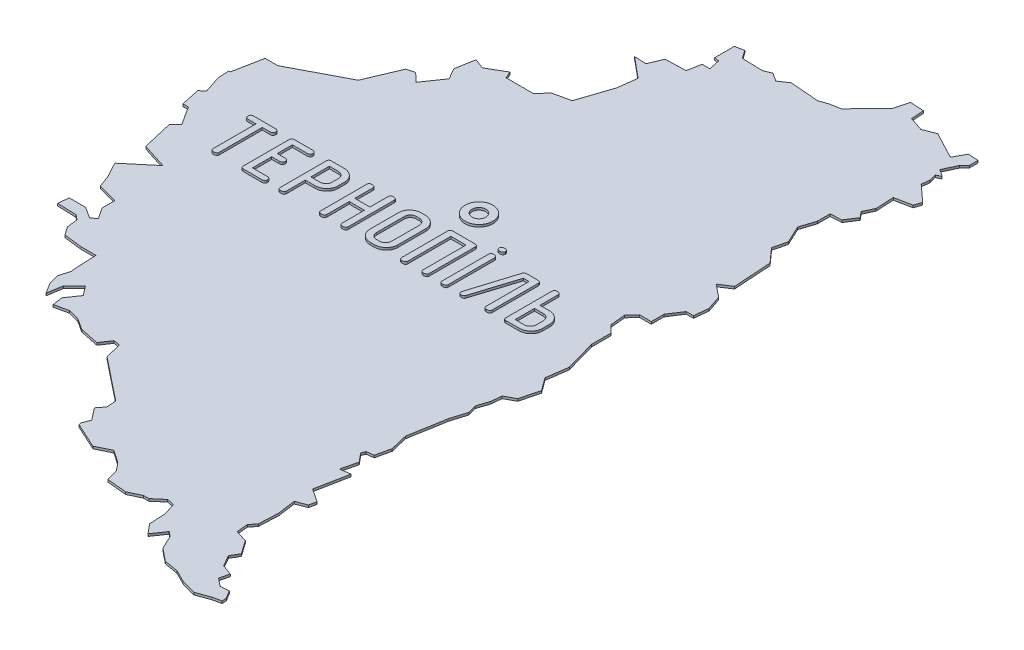
SolidWorks part; units mm, degrees
ref_plane "Спереди" through (0, 0, 0) normal (0, 0, 1) x (1, 0, 0)
ref_plane "Сверху" through (0, 0, 0) normal (0, 1, 0) x (1, 0, 0)
ref_plane "Справа" through (0, 0, 0) normal (1, 0, 0) x (0, 0, -1)
sketch "Эскиз1" plane through (0, 0, 0) normal (0, 1, 0) x (1, 0, 0)
  line B0 (-3330.514, 5782.4218) -> (-3349.3177, 5781.1264)
  line B1 (-3349.3177, 5781.1264) -> (-3366.1909, 5794.7458)
  line B2 (-3366.1909, 5794.7458) -> (-3361.0067, 5814.8703)
  line B3 (-3361.0067, 5814.8703) -> (-3383.7245, 5823.3081)
  line B4 (-3383.7245, 5823.3081) -> (-3397.344, 5847.2959)
  line B5 (-3397.344, 5847.2959) -> (-3386.9528, 5864.8295)
  line B6 (-3386.9528, 5864.8295) -> (-3407.0773, 5893.3918)
  line B7 (-3407.0773, 5893.3918) -> (-3433.0208, 5901.8272)
  line B8 (-3433.0208, 5901.8272) -> (-3434.9792, 5925.8149)
  line B9 (-3434.9792, 5925.8149) -> (-3424.5855, 5939.4598)
  line B10 (-3424.5855, 5939.4598) -> (-3422.6551, 5980.3208)
  line B11 (-3422.6551, 5980.3208) -> (-3427.8392, 6019.9372)
  line B12 (-3427.8392, 6019.9372) -> (-3405.7819, 6028.3471)
  line B13 (-3405.7819, 6028.3471) -> (-3402.5281, 6043.9249)
  line B14 (-3402.5281, 6043.9249) -> (-3431.0904, 6062.7539)
  line B15 (-3431.0904, 6062.7539) -> (-3417.4455, 6132.2001)
  line B16 (-3417.4455, 6132.2001) -> (-3439.5283, 6128.9489)
  line B17 (-3439.5283, 6128.9489) -> (-3431.0904, 6163.3303)
  line B18 (-3431.0904, 6163.3303) -> (-3446.6682, 6182.1593)
  line B19 (-3446.6682, 6182.1593) -> (-3443.4145, 6190.5947)
  line B20 (-3443.4145, 6190.5947) -> (-3427.8392, 6192.5276)
  line B21 (-3427.8392, 6192.5276) -> (-3420.6967, 6224.3411)
  line B22 (-3420.6967, 6224.3411) -> (-3429.7696, 6261.9738)
  line B23 (-3429.7696, 6261.9738) -> (-3420.6967, 6313.2538)
  line B24 (-3420.6967, 6313.2538) -> (-3416.1755, 6340.4928)
  line B25 (-3416.1755, 6340.4928) -> (-3405.7819, 6374.8996)
  line B26 (-3405.7819, 6374.8996) -> (-3410.966, 6393.7032)
  line B27 (-3410.966, 6393.7032) -> (-3402.5281, 6419.0118)
  line B28 (-3402.5281, 6419.0118) -> (-3400.5723, 6441.0946)
  line B29 (-3400.5723, 6441.0946) -> (-3378.5404, 6453.4186)
  line B30 (-3378.5404, 6453.4186) -> (-3368.1492, 6494.2796)
  line B31 (-3368.1492, 6494.2796) -> (-3388.2482, 6521.5465)
  line B32 (-3388.2482, 6521.5465) -> (-3381.7687, 6567.6399)
  line B33 (-3381.7687, 6567.6399) -> (-3400.5723, 6634.4698)
  line B34 (-3400.5723, 6634.4698) -> (-3400.5723, 6676.6542)
  line B35 (-3400.5723, 6676.6542) -> (-3416.1755, 6692.204)
  line B36 (-3416.1755, 6692.204) -> (-3419.4013, 6724.6551)
  line B37 (-3419.4013, 6724.6551) -> (-3403.8261, 6741.5258)
  line B38 (-3403.8261, 6741.5258) -> (-3378.5404, 6741.5258)
  line B39 (-3378.5404, 6741.5258) -> (-3378.5404, 6768.7927)
  line B40 (-3378.5404, 6768.7927) -> (-3359.7113, 6797.9849)
  line B41 (-3359.7113, 6797.9849) -> (-3344.1107, 6797.9849)
  line B42 (-3344.1107, 6797.9849) -> (-3340.8823, 6828.4852)
  line B43 (-3340.8823, 6828.4852) -> (-3351.276, 6859.6459)
  line B44 (-3351.276, 6859.6459) -> (-3378.5404, 6881.7185)
  line B45 (-3378.5404, 6881.7185) -> (-3354.5018, 6897.2735)
  line B46 (-3354.5018, 6897.2735) -> (-3359.7113, 6979.0513)
  line B47 (-3359.7113, 6979.0513) -> (-3386.9528, 7009.5516)
  line B48 (-3386.9528, 7009.5516) -> (-3379.8129, 7038.7616)
  line B49 (-3379.8129, 7038.7616) -> (-3397.344, 7076.3867)
  line B50 (-3397.344, 7076.3867) -> (-3386.9528, 7108.8428)
  line B51 (-3386.9528, 7108.8428) -> (-3386.9528, 7136.0767)
  line B52 (-3386.9528, 7136.0767) -> (-3362.9651, 7137.3924)
  line B53 (-3362.9651, 7137.3924) -> (-3347.3873, 7161.4005)
  line B54 (-3347.3873, 7161.4005) -> (-3357.7555, 7173.7449)
  line B55 (-3357.7555, 7173.7449) -> (-3347.3873, 7195.7921)
  line B56 (-3347.3873, 7195.7921) -> (-3349.3177, 7234.7379)
  line B57 (-3349.3177, 7234.7379) -> (-3313.6154, 7241.8677)
  line B58 (-3313.6154, 7241.8677) -> (-3308.4338, 7257.4455)
  line B59 (-3308.4338, 7257.4455) -> (-3344.1107, 7289.8914)
  line B60 (-3344.1107, 7289.8914) -> (-3342.1777, 7306.7494)
  line B61 (-3342.1777, 7306.7494) -> (-3346.0665, 7322.3349)
  line B62 (-3346.0665, 7322.3349) -> (-3335.6982, 7326.8611)
  line B63 (-3335.6982, 7326.8611) -> (-3351.276, 7337.2599)
  line B64 (-3351.276, 7337.2599) -> (-3337.6311, 7366.4775)
  line B65 (-3337.6311, 7366.4775) -> (-3327.2628, 7376.8509)
  line B66 (-3327.2628, 7376.8509) -> (-3327.2628, 7395.6596)
  line B67 (-3327.2628, 7395.6596) -> (-3349.3177, 7396.9677)
  line B68 (-3349.3177, 7396.9677) -> (-3362.9651, 7371.6515)
  line B69 (-3362.9651, 7371.6515) -> (-3420.6967, 7402.1518)
  line B70 (-3420.6967, 7402.1518) -> (-3446.6682, 7391.7708)
  line B71 (-3446.6682, 7391.7708) -> (-3477.1609, 7402.1518)
  line B72 (-3477.1609, 7402.1518) -> (-3479.1167, 7429.4136)
  line B73 (-3479.1167, 7429.4136) -> (-3508.3217, 7431.3542)
  line B74 (-3508.3217, 7431.3542) -> (-3516.757, 7400.8666)
  line B75 (-3516.757, 7400.8666) -> (-3571.2629, 7344.3973)
  line B76 (-3571.2629, 7344.3973) -> (-3593.3253, 7340.5111)
  line B77 (-3593.3253, 7340.5111) -> (-3612.1391, 7334.0138)
  line B78 (-3612.1391, 7334.0138) -> (-3673.79, 7339.2005)
  line B79 (-3673.79, 7339.2005) -> (-3693.9118, 7325.5759)
  line B80 (-3693.9118, 7325.5759) -> (-3711.4353, 7337.2599)
  line B81 (-3711.4353, 7337.2599) -> (-3728.3136, 7330.7651)
  line B82 (-3728.3136, 7330.7651) -> (-3772.4309, 7332.0656)
  line B83 (-3772.4309, 7332.0656) -> (-3784.7651, 7349.5789)
  line B84 (-3784.7651, 7349.5789) -> (-3803.5814, 7345.7003)
  line B85 (-3803.5814, 7345.7003) -> (-3803.5814, 7303.5058)
  line B86 (-3803.5814, 7303.5058) -> (-3793.1827, 7301.5704)
  line B87 (-3793.1827, 7301.5704) -> (-3788.0112, 7277.5674)
  line B88 (-3788.0112, 7277.5674) -> (-3804.8641, 7277.5674)
  line B89 (-3804.8641, 7277.5674) -> (-3810.066, 7248.3523)
  line B90 (-3810.066, 7248.3523) -> (-3854.1858, 7247.0594)
  line B91 (-3854.1858, 7247.0594) -> (-3866.5175, 7217.8494)
  line B92 (-3866.5175, 7217.8494) -> (-3892.4789, 7219.1524)
  line B93 (-3892.4789, 7219.1524) -> (-3886.6521, 7214.5982)
  line B94 (-3886.6521, 7214.5982) -> (-3847.7114, 7182.165)
  line B95 (-3847.7114, 7182.165) -> (-3852.9057, 7141.2862)
  line B96 (-3852.9057, 7141.2862) -> (-3876.9112, 7069.2467)
  line B97 (-3876.9112, 7069.2467) -> (-3914.5439, 7060.8114)
  line B98 (-3914.5439, 7060.8114) -> (-3931.4272, 7040.6946)
  line B99 (-3931.4272, 7040.6946) -> (-3991.102, 7040.6946)
  line B100 (-3991.102, 7040.6946) -> (-3997.6095, 7055.6145)
  line B101 (-3997.6095, 7055.6145) -> (-4035.2497, 7033.5673)
  line B102 (-4035.2497, 7033.5673) -> (-4057.3046, 7041.99)
  line B103 (-4057.3046, 7041.99) -> (-4064.4547, 7001.0985)
  line B104 (-4064.4547, 7001.0985) -> (-4050.825, 6977.1006)
  line B105 (-4050.825, 6977.1006) -> (-4080.0249, 6934.9087)
  line B106 (-4080.0249, 6934.9087) -> (-4098.8488, 6953.0824)
  line B107 (-4098.8488, 6953.0824) -> (-4115.7068, 6948.5383)
  line B108 (-4115.7068, 6948.5383) -> (-4146.2096, 6876.5166)
  line B109 (-4146.2096, 6876.5166) -> (-4260.4258, 6816.7987)
  line B110 (-4260.4258, 6816.7987) -> (-4287.6826, 6816.7987)
  line B111 (-4287.6826, 6816.7987) -> (-4300.0117, 6753.8498)
  line B112 (-4300.0117, 6753.8498) -> (-4303.2655, 6753.8498)
  line B113 (-4303.2655, 6753.8498) -> (-4301.9523, 6729.8367)
  line B114 (-4301.9523, 6729.8367) -> (-4289.6307, 6692.204)
  line B115 (-4289.6307, 6692.204) -> (-4300.0117, 6683.7941)
  line B116 (-4300.0117, 6683.7941) -> (-4291.5688, 6642.9077)
  line B117 (-4291.5688, 6642.9077) -> (-4279.2523, 6642.9077)
  line B118 (-4279.2523, 6642.9077) -> (-4270.817, 6629.2628)
  line B119 (-4270.817, 6629.2628) -> (-4253.9336, 6603.3167)
  line B120 (-4253.9336, 6603.3167) -> (-4267.5632, 6589.6973)
  line B121 (-4267.5632, 6589.6973) -> (-4251.9829, 6523.4769)
  line B122 (-4251.9829, 6523.4769) -> (-4197.4643, 6505.9941)
  line B123 (-4197.4643, 6505.9941) -> (-4253.9336, 6458.6028)
  line B124 (-4253.9336, 6458.6028) -> (-4237.068, 6427.4497)
  line B125 (-4237.068, 6427.4497) -> (-4226.6845, 6400.1828)
  line B126 (-4226.6845, 6400.1828) -> (-4183.855, 6388.5191)
  line B127 (-4183.855, 6388.5191) -> (-4183.855, 6361.2547)
  line B128 (-4183.855, 6361.2547) -> (-4168.2594, 6337.267)
  line B129 (-4168.2594, 6337.267) -> (-4178.6607, 6328.8037)
  line B130 (-4178.6607, 6328.8037) -> (-4202.6865, 6344.3815)
  line B131 (-4202.6865, 6344.3815) -> (-4238.3659, 6344.3815)
  line B132 (-4238.3659, 6344.3815) -> (-4240.2963, 6321.6638)
  line B133 (-4240.2963, 6321.6638) -> (-4199.4226, 6320.3684)
  line B134 (-4199.4226, 6320.3684) -> (-4189.034, 6311.933)
  line B135 (-4189.034, 6311.933) -> (-4185.7955, 6287.9199)
  line B136 (-4185.7955, 6287.9199) -> (-4173.4689, 6270.4116)
  line B137 (-4173.4689, 6270.4116) -> (-4134.5206, 6265.8625)
  line B138 (-4134.5206, 6265.8625) -> (-4102.0771, 6265.8625)
  line B139 (-4102.0771, 6265.8625) -> (-4100.134, 6224.3411)
  line B140 (-4100.134, 6224.3411) -> (-4098.8488, 6209.3983)
  line B141 (-4098.8488, 6209.3983) -> (-4105.341, 6185.3851)
  line B142 (-4105.341, 6185.3851) -> (-4098.8488, 6163.3303)
  line B143 (-4098.8488, 6163.3303) -> (-4085.2242, 6141.2476)
  line B144 (-4085.2242, 6141.2476) -> (-4080.0249, 6173.7215)
  line B145 (-4080.0249, 6173.7215) -> (-4056.0269, 6197.0996)
  line B146 (-4056.0269, 6197.0996) -> (-4040.4466, 6176.9498)
  line B147 (-4040.4466, 6176.9498) -> (-4059.2527, 6149.7083)
  line B148 (-4059.2527, 6149.7083) -> (-4056.0269, 6127.6535)
  line B149 (-4056.0269, 6127.6535) -> (-4026.8119, 6134.1076)
  line B150 (-4026.8119, 6134.1076) -> (-4002.7936, 6127.6535)
  line B151 (-4002.7936, 6127.6535) -> (-3978.7906, 6112.0757)
  line B152 (-3978.7906, 6112.0757) -> (-3937.8992, 6103.6403)
  line B153 (-3937.8992, 6103.6403) -> (-3922.9767, 6125.6951)
  line B154 (-3922.9767, 6125.6951) -> (-3909.3597, 6123.7393)
  line B155 (-3909.3597, 6123.7393) -> (-3900.264, 6088.0371)
  line B156 (-3900.264, 6088.0371) -> (-3808.1204, 6014.7276)
  line B157 (-3808.1204, 6014.7276) -> (-3806.8199, 5993.9403)
  line B158 (-3806.8199, 5993.9403) -> (-3818.4988, 5979.0254)
  line B159 (-3818.4988, 5979.0254) -> (-3798.3871, 5953.0818)
  line B160 (-3798.3871, 5953.0818) -> (-3804.8641, 5936.2086)
  line B161 (-3804.8641, 5936.2086) -> (-3803.5814, 5931.0245)
  line B162 (-3803.5814, 5931.0245) -> (-3748.4279, 5905.7159)
  line B163 (-3748.4279, 5905.7159) -> (-3717.9072, 5920.6308)
  line B164 (-3717.9072, 5920.6308) -> (-3690.6505, 5901.8272)
  line B165 (-3690.6505, 5901.8272) -> (-3677.0107, 5884.9539)
  line B166 (-3677.0107, 5884.9539) -> (-3669.8784, 5859.62)
  line B167 (-3669.8784, 5859.62) -> (-3627.7093, 5855.7312)
  line B168 (-3627.7093, 5855.7312) -> (-3601.7505, 5868.0807)
  line B169 (-3601.7505, 5868.0807) -> (-3590.0817, 5868.0807)
  line B170 (-3590.0817, 5868.0807) -> (-3568.0193, 5886.8843)
  line B171 (-3568.0193, 5886.8843) -> (-3552.4338, 5883.6585)
  line B172 (-3552.4338, 5883.6585) -> (-3544.0112, 5857.6896)
  line B173 (-3544.0112, 5857.6896) -> (-3542.063, 5821.9873)
  line B174 (-3542.063, 5821.9873) -> (-3525.1898, 5801.2254)
  line B175 (-3525.1898, 5801.2254) -> (-3506.3735, 5828.4923)
  line B176 (-3506.3735, 5828.4923) -> (-3495.9722, 5820.0544)
  line B177 (-3495.9722, 5820.0544) -> (-3482.3705, 5790.8317)
  line B178 (-3482.3705, 5790.8317) -> (-3455.1036, 5768.7769)
  line B179 (-3455.1036, 5768.7769) -> (-3424.5855, 5763.5927)
  line B180 (-3424.5855, 5763.5927) -> (-3397.344, 5749.9479)
  line B181 (-3397.344, 5749.9479) -> (-3366.1909, 5741.51)
  line B182 (-3366.1909, 5741.51) -> (-3337.6311, 5751.9291)
  line B183 (-3337.6311, 5751.9291) -> (-3319.46, 5755.7924)
  line B184 (-3319.46, 5755.7924) -> (-3320.1229, 5765.5231)
  line B185 (-3320.1229, 5765.5231) -> (-3330.514, 5782.4218)
sketch_block_instance "Блок2-1"
sketch_block "Блок2"
extrude "Бобышка-Вытянуть1" add sketch "Эскиз1" along normal blind 5 contours B184 B185 B0 B1 B2 B3 B4 B5 B6 B7 B8 B9 B10 B11 B12 B13 B14 B15 B16 B17 B18 B19 B20 B21 B22 B23 B24 B25 B26 B27 B28 B29 B30 B31 B32 B33 B34 B35 B36 B37 B38 B39 B40 B41 B42 B43 B44 B45 B46 B47 B48 region at (-3741.2235, 0, -6617.4179)
sketch "Эскиз2" plane through (0, 0, 0) normal (0, 1, 0) x (1, 0, 0)
  line L0 (-4199.7659, 6581.4744) -> (-1943.8596, 6581.4744) construction
  circle A0 centre (-3762.3406, 6753.2524) radius 15
  circle A1 centre (-3762.3406, 6753.2524) radius 30
  text T0 "ТЕРНОПІЛЬ" font "GOST Type AU" height 110
  point P6 (-4093.8474, 6581.6956)
  point P7 (-4199.7659, 6581.4744)
  dimension "D1" = 30
  dimension "D2" = 60
extrude "Бобышка-Вытянуть2" add sketch "Эскиз2" along normal blind 10
scale "Масштаб1" scale about centroid uniform scaling yes scale factor 0.05
